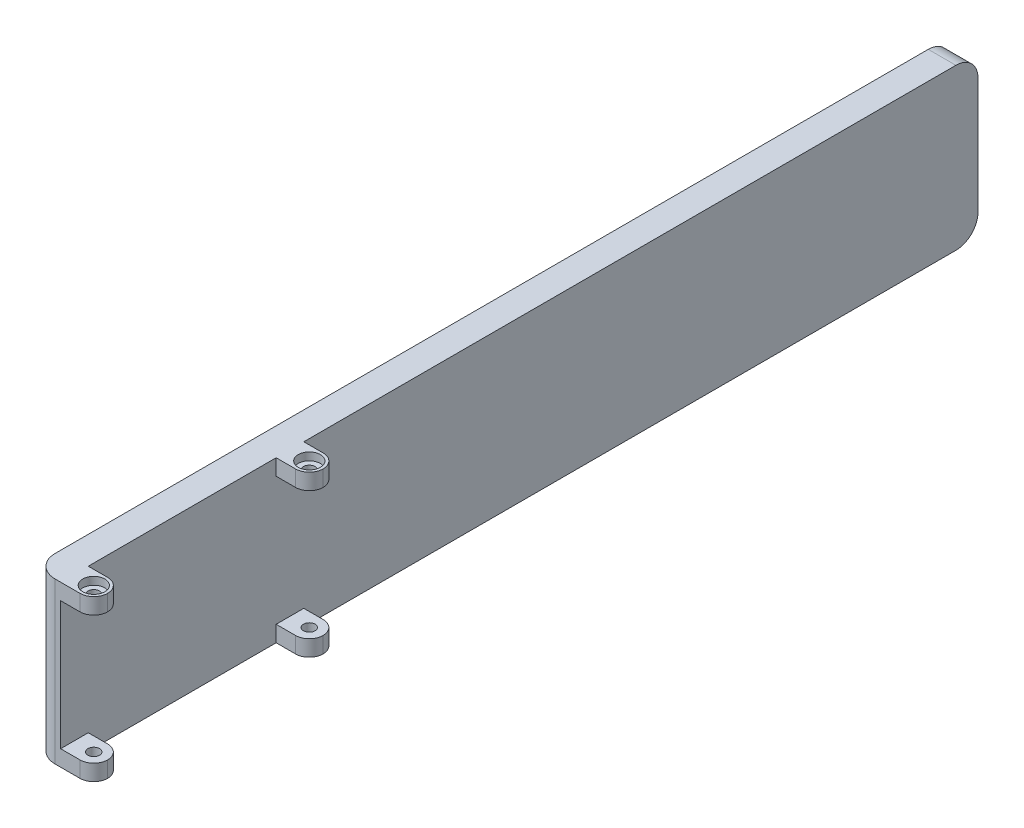
SolidWorks part; units mm, degrees
material "Esun Hard Tough Resin"
ref_plane "Front Plane" through (0, 0, 0) normal (0, 0, 1) x (1, 0, 0)
ref_plane "Top Plane" through (0, 0, 0) normal (0, 1, 0) x (1, 0, 0)
ref_plane "Right Plane" through (0, 0, 0) normal (1, 0, 0) x (0, 0, -1)
sketch "Sketch1" plane through (0, 0, 0) normal (0, 1, 0) x (1, 0, 0)
  line L1 (0, 0) -> (-5, 0)
  line L2 (0, 0) -> (0, 166)
  line L3 (0, 166) -> (-5, 166)
  line L4 (-5, 0) -> (-5, 166)
  dimension "D1" = 5
  dimension "D2" = 166
extrude "Boss-Extrude1" add sketch "Sketch1" along normal blind 29
sketch "Sketch2" plane through (0, 0, 0) normal (1, 0, 0) x (0, 0, -1)
  line L0 (0, 29) -> (166, 29) construction
  line L1 (0, 29) -> (5, 29)
  line L2 (0, 29) -> (0, 26.1)
  line L3 (0, 26.1) -> (5, 26.1)
  line L4 (5, 29) -> (5, 26.1)
  line L5 (39, 29) -> (44, 29)
  line L6 (39, 29) -> (39, 26.1)
  line L7 (39, 26.1) -> (44, 26.1)
  line L8 (44, 29) -> (44, 26.1)
  line L9 (-1000, 14.5) -> (49000, 14.5) construction
  line L10 (0, 29) -> (0, 0) construction
  line L11 (39, 2.9) -> (44, 2.9)
  line L12 (44, 0) -> (44, 2.9)
  line L13 (39, 0) -> (44, 0)
  line L14 (39, 0) -> (39, 2.9)
  line L15 (0, 2.9) -> (5, 2.9)
  line L16 (5, 0) -> (5, 2.9)
  line L17 (0, 0) -> (5, 0)
  line L18 (0, 0) -> (0, 2.9)
  point P12 (2.5, 26.1)
  point P16 (0, 14.5)
  point P17 (41.5, 26.1)
  dimension "D1" = 39
  dimension "D2" = 5
  dimension "D3" = 2.9
extrude "Boss-Extrude2" add sketch "Sketch2" along normal blind 6
sketch "Sketch3" plane through (0, 29, 0) normal (0, 1, 0) x (1, 0, 0)
  line L0 (6, 44) -> (6, 39) construction
  line L1 (6, 44) -> (6, 39) construction
  circle A0 centre (3.5, 41.5) radius 1.05
  circle A1 centre (3.5, 2.5) radius 1.05
  point P8 (6, 41.5)
  dimension "D1" = 2.1
  dimension "D2" = 39
  dimension "D3" = 2.5
extrude "Cut-Extrude1" cut sketch "Sketch3" against normal through all
sketch "Sketch4" plane through (0, 29, 0) normal (0, 1, 0) x (1, 0, 0)
  circle A0 centre (3.5, 2.5) radius 1.05 construction
  circle A1 centre (3.5, 41.5) radius 1.05 construction
  circle A2 centre (3.5, 2.5) radius 1.05 construction
  circle A3 centre (3.5, 41.5) radius 1.05 construction
  circle A4 centre (3.5, 41.5) radius 2
  circle A5 centre (3.5, 2.5) radius 2
  dimension "D1" = 4
extrude "Cut-Extrude2" cut sketch "Sketch4" against normal blind 1.4
ref_plane "Plane1" through (0, 14.5, 0) normal (0, 1, 0) x (1, 0, 0)
mirror "Mirror2" about plane through (0, 14.5, 0) normal (0, 1, 0) of "Cut-Extrude2"
fillet "Fillet1" radius 4 3 edges at (-2.5, 0, -166) (-2.5, 29, -166) (-5, 14.5, 0)
fillet "Fillet2" radius 2.5 8 edges at (6, 1.45, -5) (6, 1.45, 0) (6, 1.45, -44) (6, 1.45, -39) (6, 27.55, -44) (6, 27.55, -39) (6, 27.55, -5) (6, 27.55, 0)
